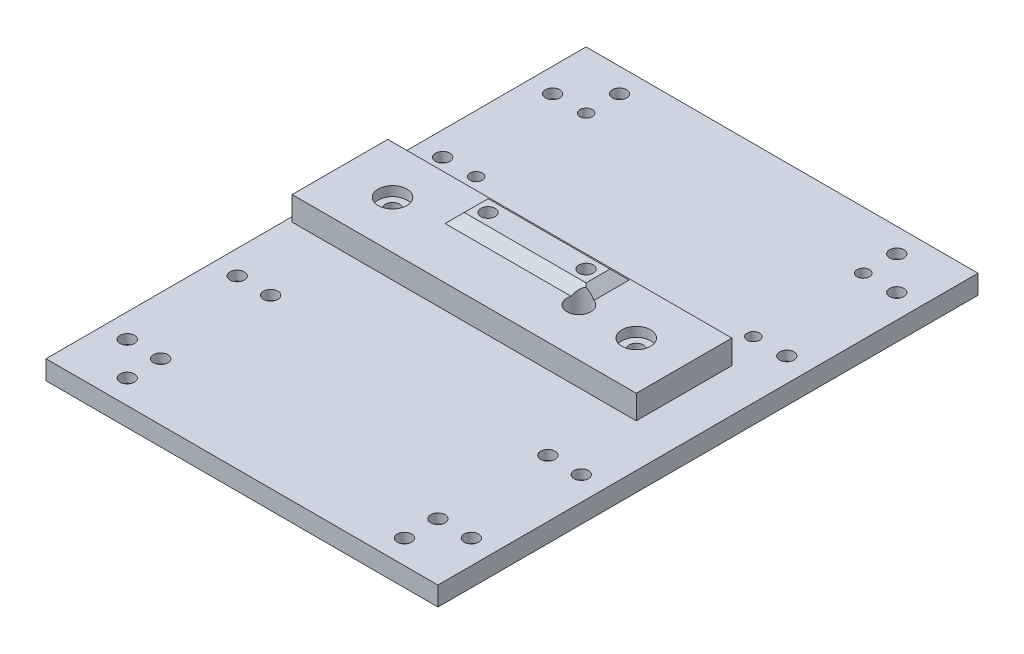
SolidWorks part; units mm, degrees
ref_plane "Front Plane" through (0, 0, 0) normal (0, 0, 1) x (1, 0, 0)
ref_plane "Top Plane" through (0, 0, 0) normal (0, 1, 0) x (1, 0, 0)
ref_plane "Right Plane" through (0, 0, 0) normal (1, 0, 0) x (0, 0, -1)
sketch "Sketch1" plane through (0, 0, 0) normal (0, 1, 0) x (1, 0, 0)
  line L0 (0, 0) -> (-19, 0) construction
  line L1 (0, 0) -> (23, 0) construction
  circle A0 centre (-25, 0) radius 6
  circle A1 centre (26, 0) radius 3
  dimension "D1" = 12
  dimension "D2" = 6
  dimension "D3" = 23
  dimension "D4" = 19
sketch "Sketch2" plane through (0, 0, 0) normal (0, 1, 0) x (1, 0, 0)
  line L0 (-36, 10) -> (-36, -10)
  line L1 (-36, -10) -> (36, -10)
  line L2 (36, -10) -> (36, 10)
  line L3 (36, 10) -> (-36, 10)
  line L4 (-31, 0) -> (-36, 0) construction
  line L5 (-36, -3.9429) -> (36, -3.9429) construction
  line L6 (0, 0) -> (-19, 0) construction
  line L7 (0, 0) -> (23, 0) construction
  circle A0 centre (-25, 0) radius 6 construction
  point P18 (0, -3.9429)
  dimension "D1" = 10
  dimension "D2" = 10
  dimension "D3" = 5
extrude "Boss-Extrude1" add sketch "Sketch2" along normal blind 5
extrude "Boss-Extrude2" add sketch "Sketch1" against normal blind 4
sketch "Sketch3" plane through (0, -4, 0) normal (0, -1, 0) x (1, 0, 0)
  circle A0 centre (-25, 0) radius 1.5
  circle A1 centre (26, 0) radius 1.5
  circle A2 centre (26, 0) radius 3 construction
  circle A3 centre (-25, 0) radius 6 construction
  dimension "D1" = 3
extrude "Cut-Extrude1" cut sketch "Sketch3" against normal through all
sketch "Sketch4" plane through (0, 5, 0) normal (0, 1, 0) x (1, 0, 0)
  circle A0 centre (-25, 0) radius 3
  circle A1 centre (26, 0) radius 3
  dimension "D1" = 6
extrude "Cut-Extrude2" cut sketch "Sketch4" against normal blind 2
sketch "Sketch5" plane through (0, 0, 0) normal (0, -1, 0) x (1, 0, 0)
  circle A0 centre (26, 0) radius 3
  circle A1 centre (26, 0) radius 4
  circle A2 centre (26, 0) radius 3 construction
  dimension "D1" = 8
extrude "Boss-Extrude3" [suppressed] add sketch "Sketch5" along normal blind 2.5
sketch "Sketch6" plane through (0, -4, 0) normal (0, -1, 0) x (1, 0, 0)
  line L0 (-36, 48.5) -> (-36, -48.5) construction
  line L1 (-36, -48.5) -> (36, -48.5) construction
  line L2 (36, -48.5) -> (36, 48.5) construction
  line L3 (36, 48.5) -> (-36, 48.5) construction
  line L4 (-36, 18.5) -> (36, 18.5) construction
  line L5 (-36, -18.5) -> (36, -18.5) construction
  line L6 (-36, -48.5) -> (-36, -56.5) construction
  line L7 (0, 18.5) -> (0, -18.5) construction
  line L8 (-36, 0) -> (36, 0) construction
  line L9 (-36, -10) -> (-36, 10) construction
  line L10 (-36, -56.5) -> (36, -56.5)
  line L11 (36, -56.5) -> (36, -48.5) construction
  line L12 (-36, 48.5) -> (-36, 56.5) construction
  line L13 (-36, 56.5) -> (36, 56.5)
  line L14 (36, 56.5) -> (36, 48.5) construction
  line L15 (-36, 56.5) -> (-41, 56.5)
  line L16 (-41, 56.5) -> (-41, -56.5)
  line L17 (-41, -56.5) -> (-36, -56.5)
  line L18 (36, -56.5) -> (41, -56.5)
  line L19 (41, -56.5) -> (41, 56.5)
  line L20 (41, 56.5) -> (36, 56.5)
  circle A0 centre (-29, -21.5) radius 1.3
  circle A2 centre (-29, -44.5) radius 1.3
  circle A3 centre (29, -44.5) radius 1.3
  circle A4 centre (29, -21.5) radius 1.3
  circle A5 centre (29, 21.5) radius 1.3 construction
  circle A6 centre (29, 44.5) radius 1.3 construction
  circle A7 centre (-29, 44.5) radius 1.3 construction
  circle A8 centre (-29, 21.5) radius 1.3 construction
  circle A9 centre (-25, 0) radius 1.5
  circle A10 centre (26, 0) radius 1.5
  circle A11 centre (26, 0) radius 1.5 construction
  circle A12 centre (-25, 0) radius 1.5 construction
  circle A13 centre (-29, 44.5) radius 1.5
  circle A14 centre (-29, 21.5) radius 1.5
  circle A15 centre (29, 21.5) radius 1.5
  circle A16 centre (29, 44.5) radius 1.5
  circle A17 centre (-29, 51.5) radius 1.5
  circle A18 centre (29, 51.5) radius 1.5
  circle A19 centre (29, -51.5) radius 1.5
  circle A20 centre (-29, -51.5) radius 1.5
  circle A21 centre (-36, 44.5) radius 1.5
  circle A22 centre (-36, 21.5) radius 1.5
  circle A23 centre (36, 44.5) radius 1.5
  circle A24 centre (36, 21.5) radius 1.5
  circle A25 centre (36, -44.5) radius 1.5
  circle A26 centre (36, -21.5) radius 1.5
  circle A27 centre (-36, -21.5) radius 1.5
  circle A28 centre (-36, -44.5) radius 1.5
  point P10 (0, 0)
  point P65 (0, 0)
  dimension "D2" = 29
  dimension "D4" = 2.6
  dimension "D5" = 23
  dimension "D8" = 3
  dimension "D11" = 3
  dimension "D12" = 7
  dimension "D13" = 5
  dimension "D1" = 37
  dimension "D3" = 3
  dimension "D6" = 4
  dimension "D7" = 4
  dimension "D9" = 8
  dimension "D10" = 8
  dimension "D14" = 6
extrude "Boss-Extrude4" add sketch "Sketch6" along normal blind 4 separate body
sketch "Sketch8" plane through (0, 0, 0) normal (0, -1, 0) x (1, 0, 0)
  circle A0 centre (14, 0) radius 2.5
  circle A1 centre (26, 0) radius 3 construction
  dimension "D1" = 5
  dimension "D2" = 12
extrude "Cut-Extrude3" cut sketch "Sketch8" against normal through all
sketch "Sketch10" plane through (0, 5, 0) normal (0, 1, 0) x (1, 0, 0)
  line L0 (-8.75, 5.25) -> (8.75, 5.25) construction
  line L1 (13, -7.5) -> (-13, -7.5) construction
  line L2 (13, -7.5) -> (13, 7.5) construction
  line L3 (13, 7.5) -> (-13, 7.5) construction
  line L4 (-13, -7.5) -> (-13, 7.5) construction
  line L5 (13, -7.5) -> (-13, 7.5) construction
  line L6 (13, 7.5) -> (-13, -7.5) construction
  line L7 (0, 5.25) -> (0, 0) construction
  line L8 (-8.75, 5.25) -> (-11.75, 5.25) construction
  line L9 (8.75, 5.25) -> (11.75, 5.25) construction
  line L10 (-10.25, 3.75) -> (-10.25, -7.5) construction
  line L11 (-10.25, 6.75) -> (-10.25, 7.5) construction
  line L12 (-11.75, 5.25) -> (-13, 5.25) construction
  circle A0 centre (-10.25, 5.25) radius 1.5
  circle A1 centre (10.25, 5.25) radius 1.5
  point P0 (0, 0)
  dimension "D3" = 23.5
  dimension "D4" = 3
  dimension "D5" = 3
  dimension "D1" = 26
  dimension "D2" = 15
  dimension "D6" = 11.25
extrude "Cut-Extrude4" cut sketch "Sketch10" against normal up to surface (5 mm away) up to face at (14, 0, -2.5)
sketch "Sketch11" plane through (0, 5, 0) normal (0, 1, 0) x (1, 0, 0)
  line L0 (-12.75, 7.75) -> (-12.75, 2.75)
  line L1 (-12.75, 2.75) -> (12.75, 2.75)
  line L2 (12.75, 2.75) -> (12.75, 7.75)
  line L3 (12.75, 7.75) -> (-12.75, 7.75)
  line L4 (0, 2.75) -> (0, 0) construction
  circle A0 centre (-10.25, 5.25) radius 1.5 construction
  circle A1 centre (10.25, 5.25) radius 1.5 construction
  circle A2 centre (-10.25, 5.25) radius 1.5
  circle A3 centre (10.25, 5.25) radius 1.5
  dimension "D1" = 2.5
  dimension "D2" = 2.5
  dimension "D3" = 2.5
extrude "Boss-Extrude6" add sketch "Sketch11" along normal blind 2
chamfer "Chamfer2" distance 2 angle 45 4 edges at (0, 5, -2.75) (12.75, 5, -5.25) (0, 5, -7.75) (-12.75, 5, -5.25)
sketch "Sketch12" plane through (0, 0, 0) normal (0, -1, 0) x (1, 0, 0)
  circle A0 centre (-10.25, -5.25) radius 3
  circle A1 centre (10.25, -5.25) radius 3
  dimension "D1" = 6
  dimension "D2" = 6
extrude "Cut-Extrude5" cut sketch "Sketch12" against normal blind 2
sketch "Sketch14" plane through (0, -8, 0) normal (0, -1, 0) x (1, 0, 0)
  line L0 (-36, 47.5) -> (-32, 47.5)
  line L1 (-36, 41.5) -> (-29, 41.5)
  line L2 (-32, 47.5) -> (-32, 51.5)
  line L3 (-26, 44.5) -> (-26, 51.5)
  line L4 (-36, 24.5) -> (-29, 24.5)
  line L5 (-36, 18.5) -> (-29, 18.5)
  line L6 (-41, 0) -> (41, 0) construction
  line L11 (0, 56.5) -> (0, -56.5) construction
  line L12 (41, 56.5) -> (-41, 56.5) construction
  line L13 (-41, -56.5) -> (41, -56.5) construction
  line L14 (36, 18.5) -> (29, 18.5)
  line L15 (36, 24.5) -> (29, 24.5)
  line L16 (26, 44.5) -> (26, 51.5)
  line L17 (32, 47.5) -> (32, 51.5)
  line L18 (36, 41.5) -> (29, 41.5)
  line L19 (36, 47.5) -> (32, 47.5)
  line L20 (36, -47.5) -> (32, -47.5)
  line L21 (36, -41.5) -> (29, -41.5)
  line L22 (32, -47.5) -> (32, -51.5)
  line L23 (26, -44.5) -> (26, -51.5)
  line L24 (36, -24.5) -> (29, -24.5)
  line L25 (36, -18.5) -> (29, -18.5)
  line L26 (-36, -18.5) -> (-29, -18.5)
  line L27 (-36, -24.5) -> (-29, -24.5)
  line L28 (-26, -44.5) -> (-26, -51.5)
  line L29 (-32, -47.5) -> (-32, -51.5)
  line L30 (-36, -41.5) -> (-29, -41.5)
  line L31 (-36, -47.5) -> (-32, -47.5)
  arc A0 (-29, 41.5) -> (-26, 44.5) centre (-29, 44.5) ccw
  arc A1 (-26, 51.5) -> (-32, 51.5) centre (-29, 51.5) ccw
  arc A2 (-36, 47.5) -> (-36, 41.5) centre (-36, 44.5) ccw
  arc A6 (-29, 18.5) -> (-29, 24.5) centre (-29, 21.5) ccw
  arc A7 (-36, 24.5) -> (-36, 18.5) centre (-36, 21.5) ccw
  circle A10 centre (-25, 0) radius 3
  circle A11 centre (26, 0) radius 3
  arc A12 (36, 24.5) -> (36, 18.5) centre (36, 21.5) cw
  arc A13 (29, 18.5) -> (29, 24.5) centre (29, 21.5) cw
  arc A14 (36, 47.5) -> (36, 41.5) centre (36, 44.5) cw
  arc A15 (26, 51.5) -> (32, 51.5) centre (29, 51.5) cw
  arc A16 (29, 41.5) -> (26, 44.5) centre (29, 44.5) cw
  arc A17 (29, -41.5) -> (26, -44.5) centre (29, -44.5) ccw
  arc A18 (26, -51.5) -> (32, -51.5) centre (29, -51.5) ccw
  arc A19 (36, -47.5) -> (36, -41.5) centre (36, -44.5) ccw
  arc A20 (29, -18.5) -> (29, -24.5) centre (29, -21.5) ccw
  arc A21 (36, -24.5) -> (36, -18.5) centre (36, -21.5) ccw
  arc A22 (-36, -24.5) -> (-36, -18.5) centre (-36, -21.5) cw
  arc A23 (-29, -18.5) -> (-29, -24.5) centre (-29, -21.5) cw
  arc A24 (-36, -47.5) -> (-36, -41.5) centre (-36, -44.5) cw
  arc A25 (-26, -51.5) -> (-32, -51.5) centre (-29, -51.5) cw
  arc A26 (-29, -41.5) -> (-26, -44.5) centre (-29, -44.5) cw
  dimension "D1" = 3
extrude "Cut-Extrude6" cut sketch "Sketch14" against normal blind 2
